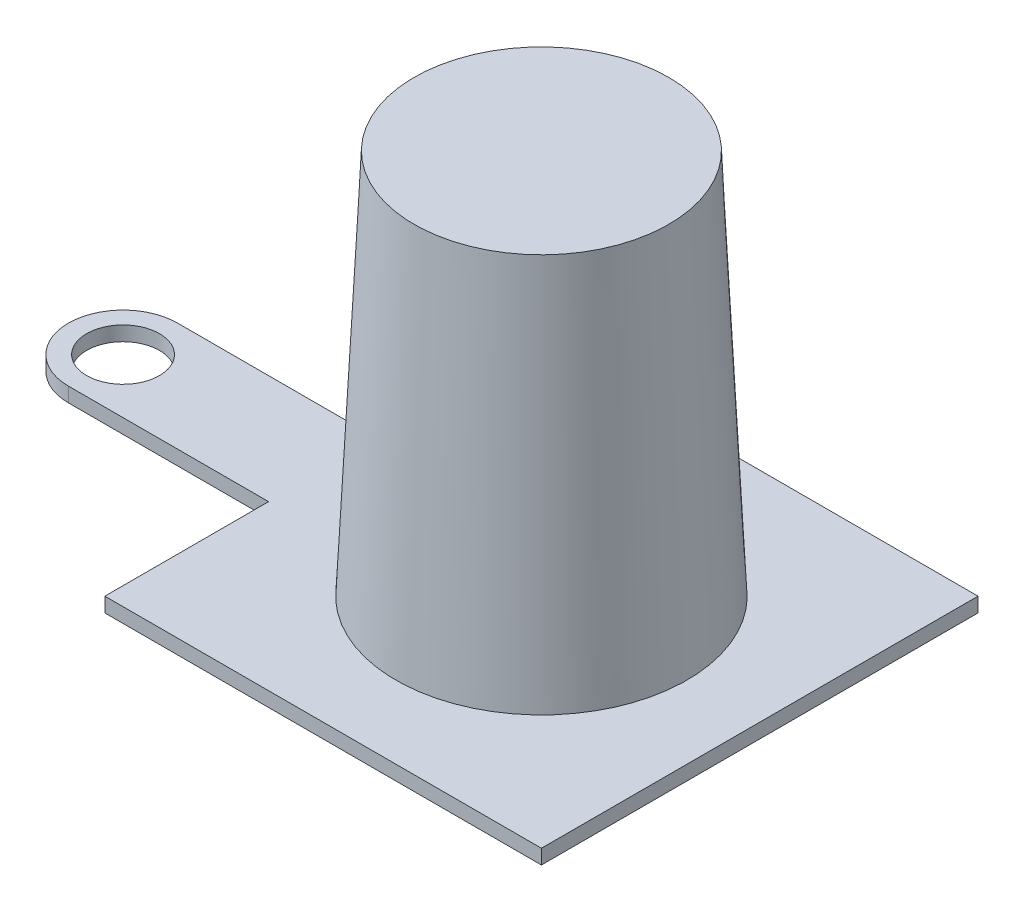
SolidWorks part; units mm, degrees
ref_plane "前视基准面" through (0, 0, 0) normal (0, 0, 1) x (1, 0, 0)
ref_plane "上视基准面" through (0, 0, 0) normal (0, 1, 0) x (1, 0, 0)
ref_plane "右视基准面" through (0, 0, 0) normal (1, 0, 0) x (0, 0, -1)
other "Configuration Table"
sketch "草图1" plane through (0, 0, 0) normal (0, 1, 0) x (1, 0, 0)
  line L1 (-6, -6) -> (6, -6)
  line L2 (-6, -6) -> (-6, 6)
  line L3 (-6, 6) -> (6, 6)
  line L4 (6, -6) -> (6, 6)
  line L5 (-6, -6) -> (6, 6) construction
  line L6 (-6, 6) -> (6, -6) construction
  line L7 (-6, 1.5) -> (-13, 1.5)
  line L8 (-6, 1.5) -> (-6, -1.5)
  line L9 (-6, -1.5) -> (-13, -1.5)
  line L10 (-13, 1.5) -> (-13, -1.5)
  circle A0 centre (0, 0) radius 4
  circle A1 centre (0, 0) radius 3.5
  circle A2 centre (-11.5, 0) radius 1
  point P12 (-13, 0)
  dimension "D1" = 8
  dimension "D2" = 7
  dimension "D7" = 2
  dimension "D3" = 12
  dimension "D4" = 3
  dimension "D5" = 7
  dimension "D6" = 1.5
extrude "凸台-拉伸1" add sketch "草图1" along normal blind 0.4 contours L1 L4 L3 L2 | L7 L10 L9 L8 | A2
extrude "凸台-拉伸2" add sketch "草图1<5>" along normal blind 10.6 from surface contours A1 starting at face at (-4.75, 0.4, 0)
sketch "草图1<5>" plane through (0, 0, 0) normal (0, 1, 0) x (1, 0, 0) same geometry as "草图1"
extrude "凸台-拉伸3" add sketch "草图1<6>" along normal blind 0.01 from surface contours A0 starting at face at (0, 0.4, -3.5)
sketch "草图1<6>" plane through (0, 0, 0) normal (0, 1, 0) x (1, 0, 0) same geometry as "草图1"
loft "放样1" add section edge at (0, 11, -3.5) section edge at (0, 0.4, -4) connector at (-3.1489, 11, 1.5279) connector at (-3.7686, 0.4, 1.3408)
fillet "圆角1" radius 1.5 2 edges at (-13, 0.2, 1.5) (-13, 0.2, -1.5)
